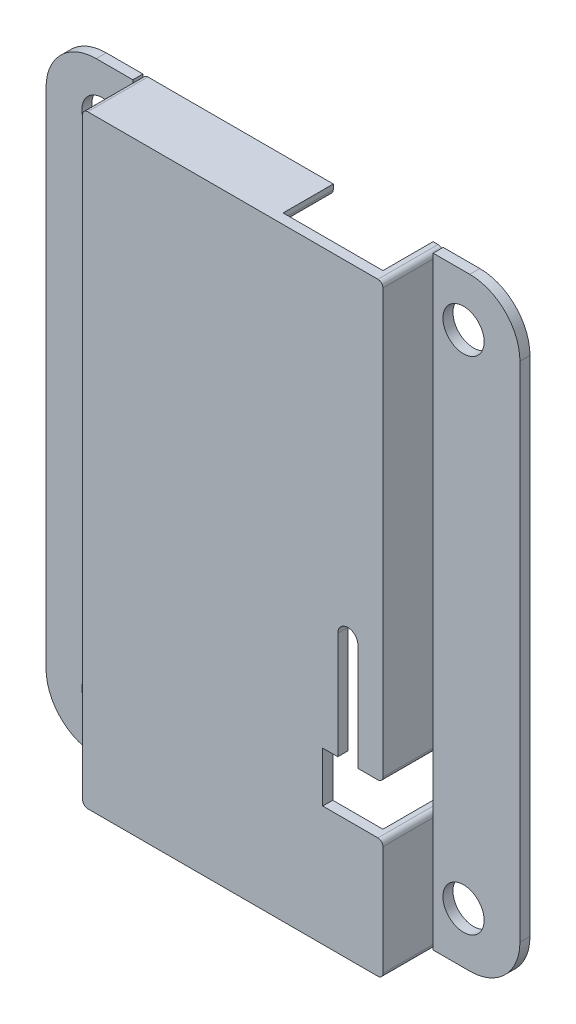
SolidWorks part; units mm, degrees
ref_plane "Front Plane" through (0, 0, 0) normal (0, 0, 1) x (1, 0, 0)
ref_plane "Top Plane" through (0, 0, 0) normal (0, 1, 0) x (1, 0, 0)
ref_plane "Right Plane" through (0, 0, 0) normal (1, 0, 0) x (0, 0, -1)
sketch "Sketch1" plane through (0, 0, 0) normal (0, 0, 1) x (1, 0, 0)
  line L0 (-7.092, 13.5001) -> (-7.092, -2.526) construction
  line L1 (-5.822, -3.796) -> (5.822, -3.796) construction
  line L2 (7.092, 0.014) -> (4.552, 0.014) construction
  line L3 (4.552, 0.014) -> (4.552, -2.526) construction
  line L4 (4.552, -2.526) -> (7.092, -2.526) construction
  line L5 (7.092, 0.014) -> (7.092, 30.3119) construction
  line L6 (4.5776, 30.3119) -> (4.5776, 17.3101) construction
  line L7 (2.0376, 14.7701) -> (-5.822, 14.7701) construction
  line L8 (7.092, 30.3119) -> (4.5776, 30.3119) construction
  line L9 (7.092, 30.3119) -> (7.092, -13.5001) construction
  line L10 (5.822, -14.7701) -> (-5.822, -14.7701) construction
  line L11 (11.9945, 12.2301) -> (11.9945, -12.2301) construction
  line L12 (0, 12.6809) -> (0, -14.7701) construction
  line L13 (-9.1387, 12.6809) -> (9.1387, 12.6809) construction
  line L14 (-9.4545, 14.7701) -> (9.4545, 14.7701) construction
  line L15 (-11.9945, 12.2301) -> (-11.9945, -12.2301) construction
  line L16 (-9.4545, -14.7701) -> (9.4545, -14.7701) construction
  line L17 (5.822, -10.4808) -> (-5.822, -10.4808) construction
  line L18 (7.092, -9.2108) -> (4.552, -9.2108) construction
  line L19 (4.552, -9.2108) -> (4.552, -6.6708) construction
  line L20 (5.8232, -7.9408) -> (5.8232, -1.256) construction
  line L21 (5.3152, -7.9408) -> (5.3152, -1.256) construction
  line L22 (6.3312, -7.9408) -> (6.3312, -1.256) construction
  line L23 (4.552, -6.6708) -> (7.092, -6.6708) construction
  line L24 (-11.9945, 0) -> (0, 0) construction
  arc A0 (-7.092, -2.526) -> (-5.822, -3.796) centre (-5.822, -2.526) ccw construction
  arc A1 (5.822, -3.796) -> (7.092, -2.526) centre (5.822, -2.526) ccw construction
  arc A2 (2.0376, 14.7701) -> (4.5776, 17.3101) centre (2.0376, 17.3101) ccw construction
  arc A3 (-5.822, 14.7701) -> (-7.092, 13.5001) centre (-5.822, 13.5001) ccw construction
  circle A4 centre (-9.1387, 12.6809) radius 1.0427 construction
  circle A5 centre (9.1387, 12.6809) radius 1.0427 construction
  circle A6 centre (9.1387, -12.6809) radius 1.0427 construction
  circle A7 centre (-9.1387, -12.6809) radius 1.0427 construction
  arc A8 (11.9945, 12.2301) -> (9.4545, 14.7701) centre (9.4545, 12.2301) ccw construction
  arc A9 (11.9945, -12.2301) -> (9.4545, -14.7701) centre (9.4545, -12.2301) cw construction
  arc A10 (-9.4545, -14.7701) -> (-11.9945, -12.2301) centre (-9.4545, -12.2301) cw construction
  arc A11 (-11.9945, 12.2301) -> (-9.4545, 14.7701) centre (-9.4545, 12.2301) cw construction
  arc A12 (5.822, -10.4808) -> (7.092, -9.2108) centre (5.822, -9.2108) ccw construction
  arc A15 (5.3152, -7.9408) -> (6.3312, -7.9408) centre (5.8232, -7.9408) ccw construction
  arc A16 (6.3312, -1.256) -> (5.3152, -1.256) centre (5.8232, -1.256) ccw construction
  point P53 (5.8232, -4.5984)
  dimension "D1" = 2.54
  dimension "D2" = 10.9741
sketch "Sketch8" plane through (0, 0, 0) normal (0, 0, 1) x (1, 0, 0)
  line L0 (6.3312, -6.6708) -> (7.6, -6.6708)
  line L1 (7.6, -6.6708) -> (7.6, 15.2781)
  line L8 (6.3312, -7.9408) -> (6.3312, -1.256) construction
  line L9 (6.3312, -6.6708) -> (6.3312, -1.256)
  line L10 (4.552, -9.2108) -> (4.552, -6.6708) construction
  line L11 (7.092, -9.2108) -> (4.552, -9.2108) construction
  line L12 (4.552, -6.6708) -> (7.092, -6.6708) construction
  line L13 (4.552, -9.2108) -> (4.552, -6.6708)
  line L14 (7.6, -9.2108) -> (4.552, -9.2108)
  line L15 (4.552, -6.6708) -> (5.3152, -6.6708)
  line L16 (5.3152, -7.9408) -> (5.3152, -1.256) construction
  line L17 (5.3152, -6.6708) -> (5.3152, -1.256)
  line L20 (-7.6, 15.2781) -> (-7.6, -15.2781)
  line L21 (7.6, -15.2781) -> (-7.6, -15.2781)
  line L22 (7.6, -15.2781) -> (7.6, -9.2108)
  line L23 (7.6, 15.2781) -> (-7.6, 15.2781)
  arc A0 (6.3312, -1.256) -> (5.3152, -1.256) centre (5.8232, -1.256) ccw construction
  arc A1 (6.3312, -1.256) -> (5.3152, -1.256) centre (5.8232, -1.256) ccw
extrude "Boss-Extrude2" add sketch "Sketch8" along normal blind 3.048 contours L23 L20 L21 L22 L14 L13 L15 L17 A1 L9 L0 L1
shell "Shell2" thickness 0.508 removed face at (3.9664, -3.9257, 0)
sketch "Sketch10" plane through (0, 15.2781, 0) normal (0, 1, 0) x (1, 0, 0)
  line L0 (7.6, 0) -> (7.092, 0) construction
  line L1 (7.092, 0) -> (2.0376, 0)
  line L2 (2.0376, 0) -> (2.0376, -2.54)
  line L3 (2.0376, -2.54) -> (7.092, -2.54)
  line L4 (7.092, -2.54) -> (7.092, 0)
  point P0 (2.0376, 0)
extrude "Cut-Extrude1" cut sketch "Sketch10" against normal up to vertex (30.0481 mm away) up to point (5.822, -14.7701, 0)
fillet "Fillet2" radius 0.254 7 edges at (-7.6, 15.2781, 1.524) (7.6, 15.2781, 1.524) (2.0376, 14.7701, 1.27) (7.6, -6.6708, 1.524) (7.6, -9.2108, 1.524) (7.6, -15.2781, 1.524) (-7.6, -15.2781, 1.524)
sketch "Sketch11" plane through (0, 0, 0) normal (0, 0, 1) x (1, 0, 0)
  line L0 (-11.9945, 12.2301) -> (-11.9945, -12.2301) construction
  line L1 (-11.9945, 12.7409) -> (-11.9945, -12.7291)
  line L2 (-7.6, 15.2809) -> (-9.4545, 15.2809)
  line L3 (-7.6, 15.0241) -> (-7.6, -15.0241) construction
  line L4 (-7.6, 15.2809) -> (-7.6, -15.2691)
  line L5 (-7.6, -15.2691) -> (-9.4545, -15.2691)
  circle A0 centre (-9.1387, 12.6809) radius 1.0427 construction
  circle A1 centre (-9.1387, 12.6809) radius 1.0427
  circle A2 centre (-9.1387, -12.6809) radius 1.0427 construction
  circle A3 centre (-9.1387, -12.6809) radius 1.0427
  arc A4 (-11.9945, -12.7291) -> (-9.4545, -15.2691) centre (-9.4545, -12.7291) ccw
  arc A5 (-11.9945, 12.7409) -> (-9.4545, 15.2809) centre (-9.4545, 12.7409) cw
  dimension "D1" = 2.54
extrude "Boss-Extrude3" add sketch "Sketch11" along normal blind 0.508
mirror "Mirror1" about plane through (0, 0, 0) normal (1, 0, 0) of "Boss-Extrude3"
